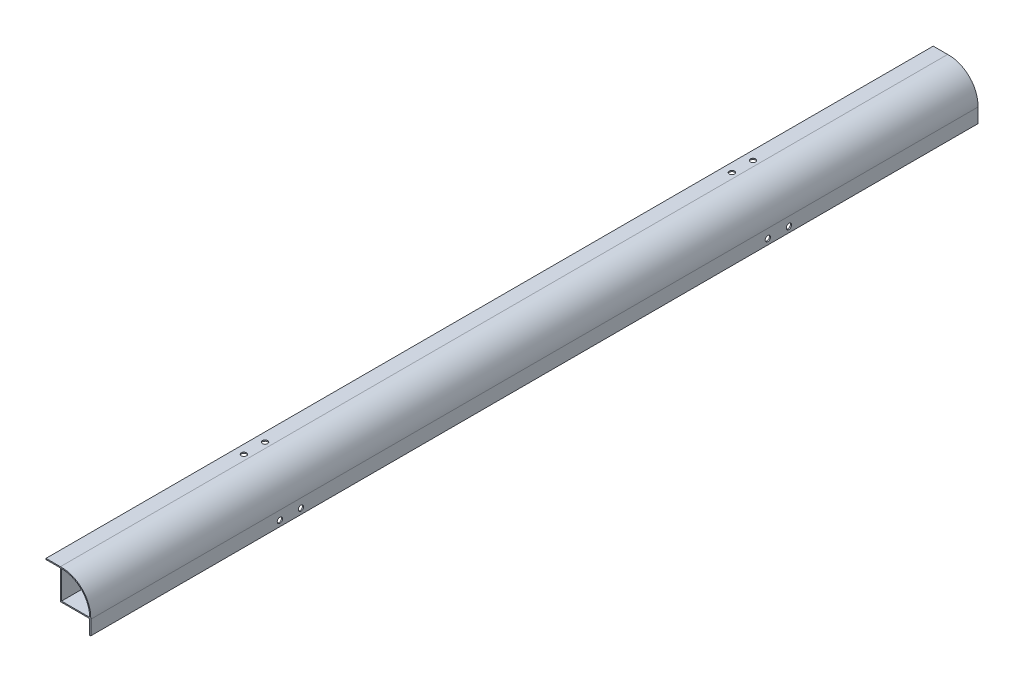
SolidWorks part; units mm, degrees
ref_plane "Alzado" through (0, 0, 0) normal (0, 0, 1) x (1, 0, 0)
ref_plane "Planta" through (0, 0, 0) normal (0, 1, 0) x (1, 0, 0)
ref_plane "Vista lateral" through (0, 0, 0) normal (1, 0, 0) x (0, 0, -1)
sketch "Croquis1" plane through (0, 0, 0) normal (0, 0, 1) x (1, 0, 0)
  line L0 (-13.7, -13.7) -> (13.6811, -13.7)
  line L1 (-12.7, -12.7) -> (12.7, -12.7)
  line L2 (-12.7, -12.7) -> (-12.7, 12.7)
  line L5 (0, 16.5842) -> (0, -23.118) construction
  line L6 (-13.7, -13.7) -> (-13.7, 13.6811)
  line L8 (-18.0998, 0) -> (17.5647, 0) construction
  line L9 (13.6811, -13.7) -> (12.6811, -13.7)
  line L10 (13.6811, -13.7) -> (13.6811, -26.7)
  line L11 (13.6811, -26.7) -> (12.6811, -26.7)
  line L12 (12.6811, -13.7) -> (12.6811, -26.7)
  line L13 (-13.7, 13.6811) -> (-26.7, 13.6811)
  line L14 (-13.7, 13.6811) -> (-13.7, 12.6811)
  line L15 (-13.7, 12.6811) -> (-26.7, 12.6811)
  line L16 (-26.7, 13.6811) -> (-26.7, 12.6811)
  arc A0 (-12.7, 12.7) -> (12.7, -12.7) centre (-12.7, -12.7) cw
  arc A1 (-13.7, 13.6811) -> (13.6811, -13.7) centre (-12.7, -12.7) cw
  point P0 (0, 0)
  point P12 (-12.7, 0)
  point P13 (0, -12.7)
  dimension "D3" = 25.4
  dimension "D1" = 25.4
  dimension "D2" = 25.4
  dimension "D5" = 1
  dimension "D6" = 13
  dimension "D7" = 1
  dimension "D8" = 13
  dimension "D4" = 1
extrude "Saliente-Extruir1" add sketch "Croquis1" along normal mid plane 800 contours A1 L6 L0 L2 A0 L1 | L13 L16 L15 L6 | L0 L12 L11 L10 region at (-13.3125, -0.5095, 0) region at (13.1811, -20.2, 0) region at (-20.2, 13.1811, 0)
sketch "Croquis2" plane through (0, 13.6811, 0) normal (0, 1, 0) x (1, 0, 0)
  line L0 (119.3875, 0) -> (-118.4797, 0) construction
  line L1 (-29.9629, -220) -> (20.492, -220) construction
  line L2 (-26.7, -400) -> (-26.7, 400) construction
  line L3 (-13.7, -400) -> (13.7, -400) construction
  line L4 (-29.9629, 220) -> (20.492, 220) construction
  circle A0 centre (-18.7, -210.5) radius 2.3813
  circle A1 centre (-18.7, -229.5) radius 2.3813
  circle A2 centre (-18.7, 229.5) radius 2.3813
  circle A3 centre (-18.7, 210.5) radius 2.3813
  dimension "D1" = 4.7625
  dimension "D2" = 9.5
  dimension "D3" = 8
  dimension "D4" = 180
extrude "Cortar-Extruir1" cut sketch "Croquis2" against normal blind 10
sketch "Croquis3" plane through (13.6811, 0, 0) normal (1, 0, 0) x (0, 0, -1)
  line L0 (0, 76.9116) -> (0, -92.6451) construction
  line L1 (-220, 38.7463) -> (-220, -62.7421) construction
  line L2 (-400, 13.7) -> (-400, -13.7) construction
  line L3 (-400, -26.7) -> (400, -26.7) construction
  line L4 (220, 38.7463) -> (220, -62.7421) construction
  circle A0 centre (-210.5, -21.7) radius 2.3813
  circle A1 centre (-229.5, -21.7) radius 2.3813
  circle A2 centre (-210.5, -21.7) radius 2.3813
  circle A3 centre (-229.5, -21.7) radius 2.3813
  circle A4 centre (229.5, -21.7) radius 2.3813
  circle A5 centre (210.5, -21.7) radius 2.3813
  dimension "D1" = 4.7625
  dimension "D2" = 180
  dimension "D3" = 9.5
  dimension "D4" = 5
extrude "Cortar-Extruir2" cut sketch "Croquis3" against normal blind 10 contours A1 | A0 | A5 | A4 region at (13.6811, -21.7, 210.5) region at (13.6811, -21.7, 229.5) region at (13.6811, -21.7, -229.5) region at (13.6811, -21.7, -210.5)
